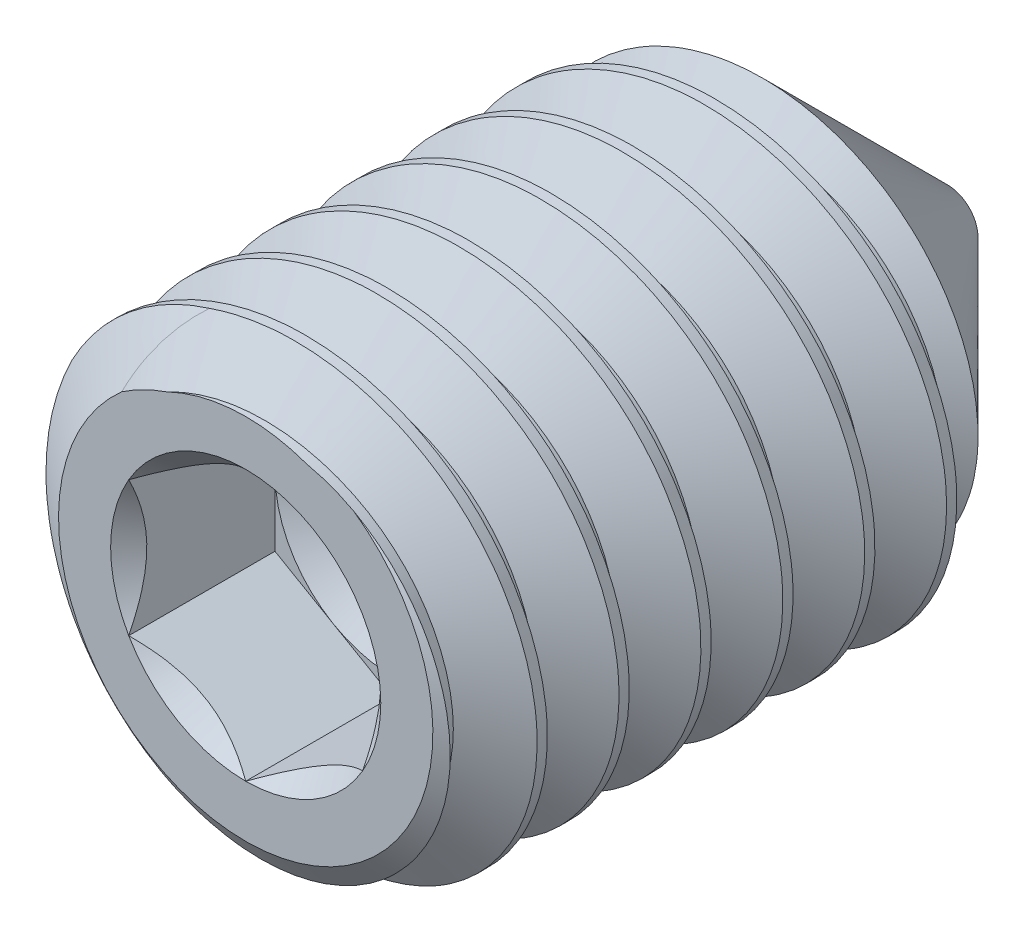
SolidWorks part; units mm, degrees
ref_plane "Front" through (0, 0, 0) normal (0, 0, 1) x (1, 0, 0)
ref_plane "Top" through (0, 0, 0) normal (0, 1, 0) x (1, 0, 0)
ref_plane "Right" through (0, 0, 0) normal (1, 0, 0) x (0, 0, -1)
sketch "Body Sketch" plane through (0, 0, 0) normal (1, 0, 0) x (0, 0, -1)
  line L0 (-3, 0) -> (-3, 1.6)
  line L1 (-3, 1.6) -> (-2.7199, 2)
  line L2 (-2.7199, 2) -> (1.26, 2)
  line L3 (1.26, 2) -> (3, 0.26)
  line L4 (-3, 1.6) -> (-3, -1.6) construction
  line L5 (3, 0) -> (-3, 0)
  line L6 (0, 2) -> (0, -2) construction
  line L8 (3, 0.26) -> (3, 0)
  line L9 (-3, -2) -> (3, -2) construction
  line L10 (3, 0.26) -> (3, -0.26) construction
  line L11 (3, -0.26) -> (1.26, -2) construction
  line L13 (3, 0.26) -> (2.74, 0) construction
  line L15 (2.74, 0) -> (3, -0.26) construction
  dimension "D3" = 35
  dimension "D7" = 3.2
  dimension "Diameter" = 4
  dimension "Length" = 6
  dimension "D2" = 0.52
  dimension "Cone Angle" = 90
  dimension "D90" = 90
revolve "Body Revolve" add sketch "Body Sketch" angle 360 about L5
ref_plane "Tip Plane" through (0, 0, -3) normal (0, 0, 1) x (1, 0, 0)
sketch "Spiral Sketch" plane through (0, 0, -3) normal (0, 0, 1) x (1, 0, 0)
  circle A0 centre (0, 0) radius 2 construction
  circle A1 centre (0, 0) radius 2
sketch "Hex Sketch" plane through (0, 0, 3) normal (0, 0, 1) x (1, 0, 0)
  line L1 (0, 1.1547) -> (-1, 0.5774)
  line L2 (-1, 0.5774) -> (-1, -0.5774)
  line L3 (-1, -0.5774) -> (0, -1.1547)
  line L4 (0, -1.1547) -> (1, -0.5774)
  line L5 (1, -0.5774) -> (1, 0.5774)
  line L6 (1, 0.5774) -> (0, 1.1547)
  circle A0 centre (0, 0) radius 1 construction
  dimension "Hex" = 2
extrude "Hex Extrude" cut sketch "Hex Sketch" against normal blind 1.25
sketch "Hex Entry Sketch" plane through (0, 0, 3) normal (0, 0, 1) x (1, 0, 0)
  circle A0 centre (0, 0) radius 1.1547
extrude "Hex Entry Extrude" cut sketch "Hex Entry Sketch" against normal through all draft 45
sketch "Hex Bottom Sketch" plane through (0, 0, 1.75) normal (0, 0, 1) x (1, 0, 0)
  circle A0 centre (0, 0) radius 1 construction
  circle A1 centre (0, 0) radius 1
extrude "Hex Bottom Extrude" cut sketch "Hex Bottom Sketch" against normal through all draft 60
curve "Helix/Spiral" pitch 0.7 height 6.7 radius 2 centre (0, 0, -3) axis (0, 0, 1) start towards (0, 1, 0)
sketch "Sketch28" plane through (0, 0, 0) normal (1, 0, 0) x (0, 0, -1)
  line L0 (3, 2) -> (3.6125, 2)
  line L1 (3.6125, 2) -> (3.35, 1.5453)
  line L2 (3.35, 1.5453) -> (3.2625, 1.5453)
  line L3 (3.2625, 1.5453) -> (3, 2)
  line L4 (3.1313, 1.7727) -> (3.4813, 1.7727) construction
  line L6 (-2.7199, 2) -> (1.26, 2) construction
  line L7 (3, 6.7518) -> (3, -6.7518) construction
  dimension "D1" = 0.0875
  dimension "D3" = 60
  dimension "D2" = 0.35
sweep "Thread Sweep" cut profiles "Sketch28" path "Helix/Spiral"
ref_plane "Contact Plane 1" through (0, 0, 3) normal (0, 0, 1) x (1, 0, 0)
ref_plane "Contact Plane 2" through (0, 0, -3) normal (0, 0, -1) x (-1, 0, 0)
ref_axis "Center Axis 1" through (0, 0, 48.3835) along (0, 0, -1)
equation "\"D7@Body Sketch\" = \"Diameter@Body Sketch\" * .8"
equation "\"D1@Sketch28\" = \"D4@Helix/Spiral\" * .125"
equation "\"D3@Helix/Spiral\" = \"Length@Body Sketch\" + \"D4@Helix/Spiral\""
equation "\"hex Depth@Hex Extrude\" = \"Hex@Hex Sketch\" * .625"
equation "\"D2@Sketch28\" = \"D4@Helix/Spiral\" * .5"
equation "\"D2@Body Sketch\" = \"Diameter@Body Sketch\" * .13"
equation "\"D90@Body Sketch\" = \"Cone Angle@Body Sketch\""
equation "\"Diameter\"= 4mm"
equation "\"Thread Pitch\"= 0.7mm"
equation "\"Hex Size\"= 2.0mm"
equation "\"Diameter@Body Sketch\" = \"Diameter\""
equation "\"Hex@Hex Sketch\" = \"Hex Size\""
equation "\"D4@Helix/Spiral\"=\"Thread Pitch\""
